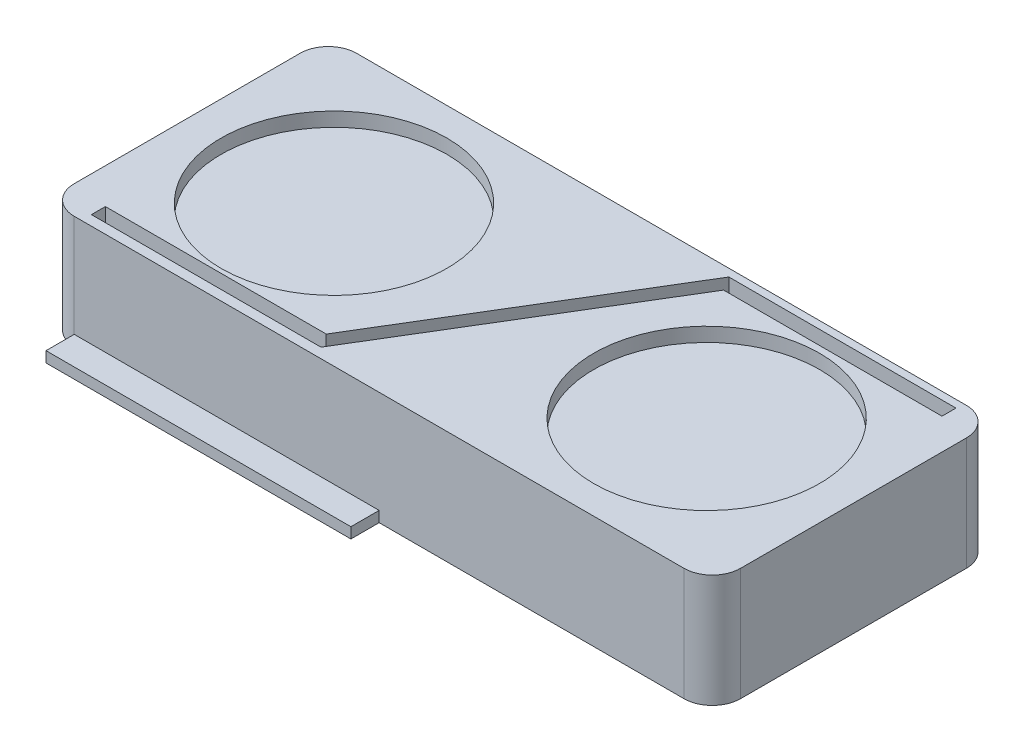
SolidWorks part; units mm, degrees
ref_plane "Front Plane" through (0, 0, 0) normal (0, 0, 1) x (1, 0, 0)
ref_plane "Top Plane" through (0, 0, 0) normal (0, 1, 0) x (1, 0, 0)
ref_plane "Right Plane" through (0, 0, 0) normal (1, 0, 0) x (0, 0, -1)
sketch "Sketch1" plane through (0, 0, 0) normal (0, 1, 0) x (1, 0, 0)
  line L1 (-118, 50) -> (118, 50)
  line L2 (-118, 50) -> (-118, -50)
  line L3 (-118, -50) -> (118, -50)
  line L4 (118, 50) -> (118, -50)
  line L5 (-118, 50) -> (118, -50) construction
  line L6 (-118, -50) -> (118, 50) construction
  point P0 (0, 0)
  dimension "D1" = 236
  dimension "D2" = 100
extrude "Boss-Extrude1" add sketch "Sketch1" along normal blind 40
sketch "Sketch2" plane through (0, 40, 0) normal (0, 1, 0) x (1, 0, 0)
  line L4 (0, -2) -> (0, 2)
  line L8 (-66, 0) -> (0, 0) construction
  line L9 (0, 0) -> (66, 0) construction
  circle A0 centre (-66, 0) radius 40
  circle A1 centre (66, 0) radius 40
  dimension "D2" = 80
  dimension "D1" = 66
  dimension "D3" = 4
extrude "Cut-Extrude1" cut sketch "Sketch2" against normal blind 5 contours A0 | A1 region at (-66, 40, 0) region at (66, 40, 0)
fillet "Fillet1" radius 10 4 edges at (118, 20, 50) (118, 20, -50) (-118, 20, 50) (-118, 20, -50)
sketch "Sketch3" plane through (0, 40, 0) normal (0, 1, 0) x (1, 0, 0)
  line L0 (-105.4631, -41.5021) -> (-105.4631, -46.455)
  line L1 (-105.4631, -46.455) -> (-24.1389, -46.455)
  line L2 (-24.1389, -46.455) -> (29.6601, 42.356)
  line L3 (29.6601, 42.356) -> (107.0002, 42.356)
  line L4 (107.0002, 42.356) -> (107.0002, 47.309)
  line L5 (107.0002, 47.309) -> (26.5579, 47.309)
  line L6 (26.5579, 47.309) -> (-27.2411, -41.5021)
  line L7 (-27.2411, -41.5021) -> (-105.4631, -41.5021)
  point P2 (-27.2411, -41.5021)
extrude "Cut-Extrude2" cut sketch "Sketch3" against normal blind 10
sketch "Sketch4" plane through (0, 0, 50) normal (0, 0, 1) x (1, 0, 0)
  line L1 (-108, 0) -> (0, 0)
  line L2 (-108, 0) -> (-108, 3.7749)
  line L3 (-108, 3.7749) -> (0, 3.7749)
  line L4 (0, 0) -> (0, 3.7749)
extrude "Boss-Extrude2" add sketch "Sketch4" along normal blind 10
